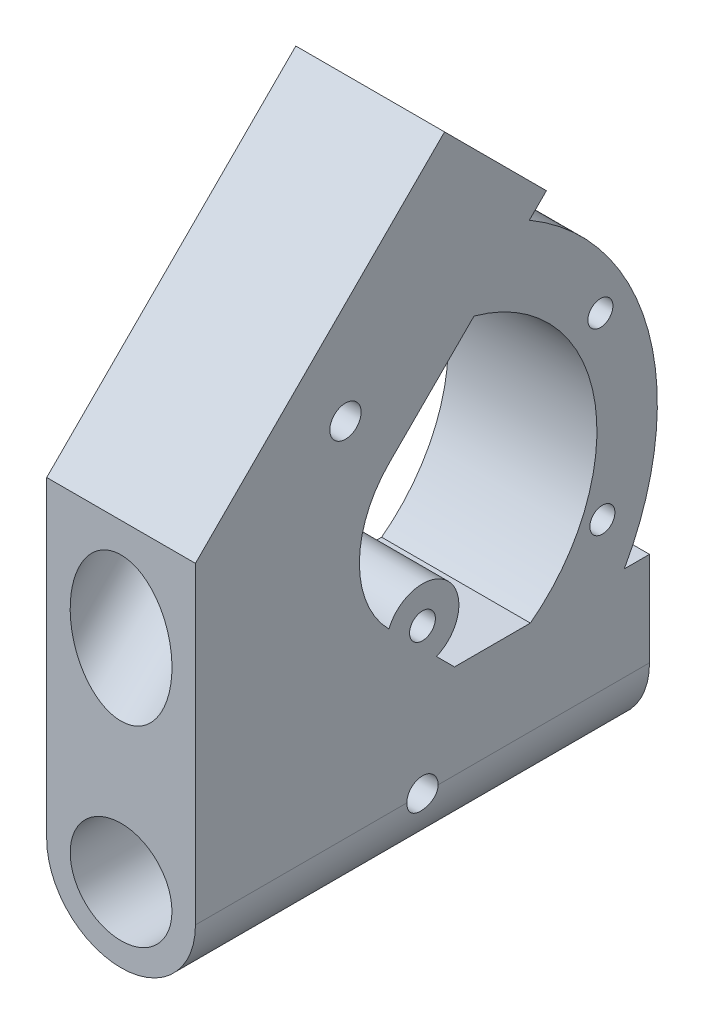
SolidWorks part; units mm, degrees
ref_plane "Alzado" through (0, 0, 0) normal (0, 0, 1) x (1, 0, 0)
ref_plane "Planta" through (0, 0, 0) normal (0, 1, 0) x (1, 0, 0)
ref_plane "Vista lateral" through (0, 0, 0) normal (1, 0, 0) x (0, 0, -1)
sketch "Croquis1" plane through (0, 0, 0) normal (0, 0, 1) x (1, 0, 0)
  line L0 (0, 0) -> (0, -10) construction
  line L4 (0, 0) -> (0, 12) construction
  line L5 (-9.5, 12) -> (9.5, 12)
  line L6 (-9.5, 12) -> (-9.5, 0)
  line L7 (9.5, 12) -> (9.5, 0)
  circle A0 centre (0, 0) radius 6.5
  arc A2 (-9.5, 0) -> (9.5, 0) centre (0, 0) ccw
  point P8 (0, -10)
  point P9 (0, 12)
  dimension "D1" = 13
  dimension "D2" = 3
  dimension "D4" = 12
extrude "Saliente-Extruir1" add sketch "Croquis1" against normal mid plane 58
sketch "Croquis2" plane through (0, 0, 0) normal (1, 0, 0) x (0, 0, -1)
  line L0 (-29, 12) -> (-29, 40)
  line L1 (-29, 40) -> (2.8198, 71.8198)
  line L2 (2.8198, 71.8198) -> (15.8306, 58.809)
  line L3 (29, 12) -> (-29, 12) construction
  line L4 (-29, 12) -> (4.0901, 12)
  line L5 (15.8306, 58.809) -> (-4.2518, 38.7267)
  line L6 (-4.2518, 20.3419) -> (4.0901, 12)
  line L7 (-29, 12) -> (34.2159, 75.2159) construction
  arc A0 (-4.2518, 20.3419) -> (-4.2518, 38.7267) centre (4.9406, 29.5343) cw
  dimension "D4" = 135
  dimension "D5" = 13
  dimension "D1" = 28
  dimension "D2" = 45
  dimension "D3" = 18.4
  dimension "D6" = 45
extrude "Saliente-Extruir2" add sketch "Croquis2" along normal mid plane 19
ref_plane "Plano1" through (0, 37.3198, -37.3198) normal (0, 0.7071, -0.7071) x (-1, 0, 0)
sketch "Croquis3" plane through (0, 37.3198, -37.3198) normal (0, 0.7071, -0.7071) x (1, 0, 0)
  line L0 (0, -48.7904) -> (0, -30.3904) construction
  line L1 (9.5, -48.7904) -> (-9.5, -48.7904) construction
  line L4 (9.5, -30.3904) -> (-9.5, -30.3904) construction
  circle A0 centre (0, -39.5904) radius 6.5
  dimension "D1" = 13
extrude "Cortar-Extruir1" cut sketch "Croquis3" against normal blind 73
sketch "Croquis4" plane through (0, 0, 0) normal (1, 0, 0) x (0, 0, -1)
  line L0 (-4.2518, 38.7267) -> (15.8306, 58.809) construction
  line L1 (29, 12) -> (4.0901, 12) construction
  line L2 (6.5823, 49.5608) -> (13.6534, 56.6319)
  line L3 (13.7825, 12) -> (25.7825, 12)
  line L4 (15.8306, 58.809) -> (2.8198, 71.8198) construction
  line L5 (29, 0) -> (29, 12) construction
  arc A0 (6.5823, 49.5608) -> (13.7825, 12) centre (1, 29.0202) cw
  arc A1 (13.6534, 56.6319) -> (25.7825, 12) centre (-3, 28.1421) cw
  dimension "D3" = 33
  dimension "D4" = 4
  dimension "D5" = 35
  dimension "D6" = 32
  dimension "D1" = 10
  dimension "D2" = 12
extrude "Saliente-Extruir3" add sketch "Croquis4" along normal mid plane 19
sketch "Croquis5" plane through (0, 0, 0) normal (1, 0, 0) x (0, 0, -1)
  circle A0 centre (0, 18.5926) radius 4.65
  circle A1 centre (0, 18.5926) radius 1.65
  dimension "D1" = 3.3
  dimension "D2" = 3
extrude "Saliente-Extruir4" add sketch "Croquis5" along normal mid plane 19
sketch "Croquis6" plane through (0, 0, 0) normal (1, 0, 0) x (0, 0, -1)
  circle A0 centre (22.7263, 41.8254) radius 1.6
  circle A1 centre (22.98, 18.8454) radius 1.6
  circle A2 centre (0, 18.5926) radius 1.65 construction
  dimension "D1" = 3.2
  dimension "D2" = 22.98
  dimension "D3" = 32.5
  dimension "D4" = 22.98
extrude "Cortar-Extruir2" cut sketch "Croquis6" against normal mid plane 30 contours A0 | A1
sketch "Croquis7" plane through (0, 0, 0) normal (1, 0, 0) x (0, 0, -1)
  line L0 (9.3252, 65.3144) -> (-29, 26.9892) construction
  line L1 (15.8306, 58.809) -> (2.8198, 71.8198) construction
  line L2 (-29, 40) -> (-29, 0) construction
  circle A0 centre (0, 0) radius 2
  circle A2 centre (-9.8374, 46.1518) radius 2
  dimension "D1" = 4
extrude "Cortar-Extruir3" cut sketch "Croquis7" against normal mid plane 53
